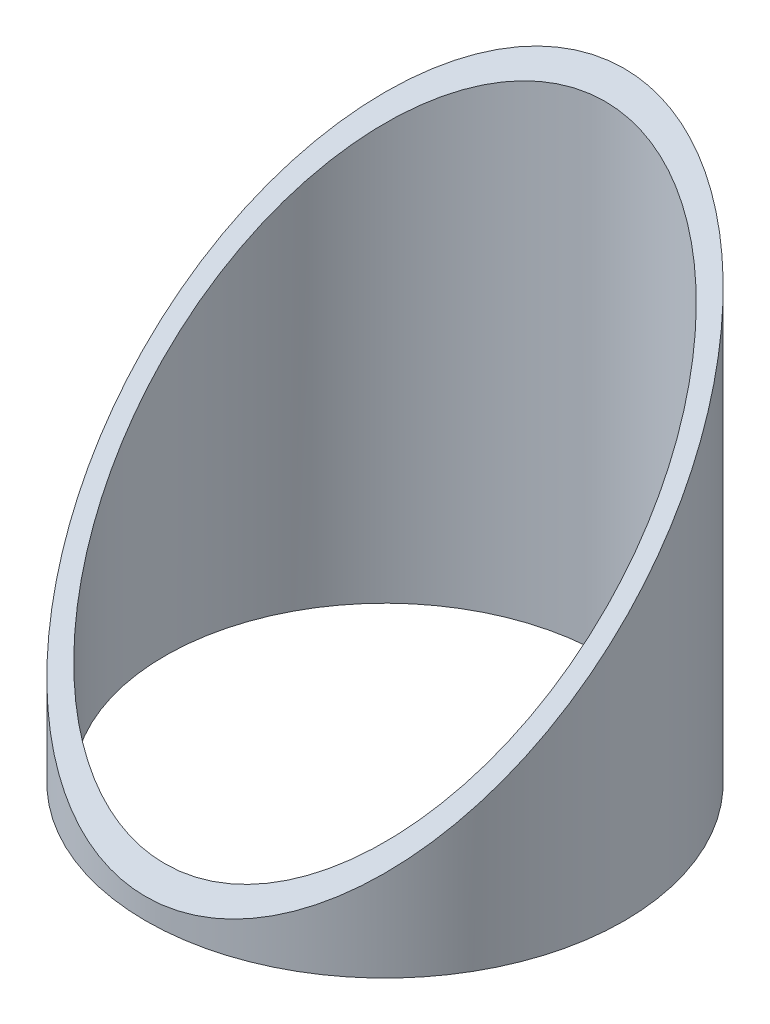
SolidWorks part; units mm, degrees
material "1060 Alloy"
ref_plane "Front Plane" through (0, 0, 0) normal (0, 0, 1) x (1, 0, 0)
ref_plane "Top Plane" through (0, 0, 0) normal (0, 1, 0) x (1, 0, 0)
ref_plane "Right Plane" through (0, 0, 0) normal (1, 0, 0) x (0, 0, -1)
sketch "Sketch1" plane through (0, 0, 0) normal (0, 1, 0) x (1, 0, 0)
  line L0 (-102.6662, 0) -> (114.9528, 0) construction
  line L1 (-55, 0) -> (55, 0) construction
ref_plane "Plane1" through (0, 0, 0) normal (0, 0.7071, 0.7071) x (1, 0, 0)
sketch "Sketch2" plane through (0, 0, 0) normal (0, 0.7071, 0.7071) x (1, 0, 0)
  circle A0 centre (0, 20) radius 20
  dimension "D1" = 40
extrude "Boss-Extrude1" add sketch "Sketch2" against normal blind 0.7071
ref_plane "Plane2" through (0, -3.25, 0) normal (0, 1, 0) x (1, 0, 0)
sketch "Sketch3" plane through (0, -3.25, 0) normal (0, 1, 0) x (1, 0, 0)
  line L0 (0, -15.8313) -> (0, 15.8313) construction
  circle A0 centre (0, 7.4) radius 7.4
  circle A1 centre (0, 7.4) radius 5.9
  dimension "D1" = 14.8
  dimension "D2" = 11.8
extrude "Boss-Extrude2" add sketch "Sketch3" along normal blind 1 separate body
sketch "Sketch4" plane through (0, -3.25, 0) normal (0, -1, 0) x (1, 0, 0)
  line L1 (-145.8552, 47.5561) -> (159.3648, 47.5561)
  line L2 (-145.8552, 47.5561) -> (-145.8552, -79.3149)
  line L3 (-145.8552, -79.3149) -> (159.3648, -79.3149)
  line L4 (159.3648, 47.5561) -> (159.3648, -79.3149)
  circle A3 centre (0, -7.4) radius 6.4
  circle A4 centre (0, -7.4) radius 7.4 construction
  dimension "D1" = 12.8
  dimension "D2" = 0
extrude "Cut-Extrude1" cut sketch "Sketch4" against normal through all both and the other way through all
sketch "Sketch5" plane through (0, -2.25, 0) normal (0, 1, 0) x (1, 0, 0)
  circle A1 centre (0, 7.4) radius 6.28
  circle A2 centre (0, 7.4) radius 7.4 construction
  circle A3 centre (0, 7.4) radius 5.78
  dimension "D1" = 12.56
  dimension "D3" = 11.56
  dimension "D2" = 0
extrude "Boss-Extrude3" add sketch "Sketch5" along normal up to next separate body
sketch "Sketch7" plane through (0, 0, 0) normal (0, 0.7071, 0.7071) x (1, 0, 0)
  circle A0 centre (0, 10.4652) radius 18.2827
extrude "Cut-Extrude3" cut sketch "Sketch7" against normal up to surface (0.7071 mm away) up to face at (0, 0, -1)
sketch "Sketch8" plane through (0, -3.25, 0) normal (0, -1, 0) x (1, 0, 0)
  circle A0 centre (0, -7.3953) radius 12.7728
extrude "Cut-Extrude4" cut sketch "Sketch8" against normal blind 2.82
